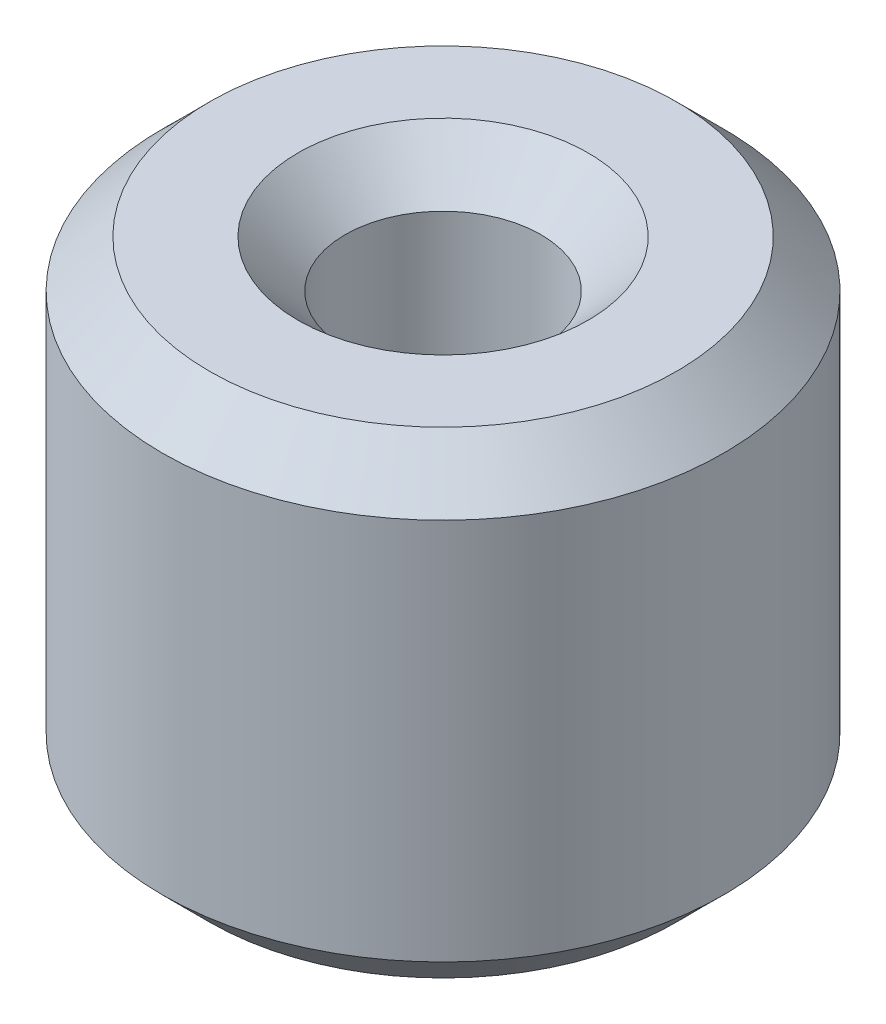
SolidWorks part; units mm, degrees
ref_plane "Front Plane" through (0, 0, 0) normal (0, 0, 1) x (1, 0, 0)
ref_plane "Top Plane" through (0, 0, 0) normal (0, 1, 0) x (1, 0, 0)
ref_plane "Right Plane" through (0, 0, 0) normal (1, 0, 0) x (0, 0, -1)
sketch "Sketch1" plane through (0, 0, 0) normal (0, 1, 0) x (1, 0, 0)
  circle A0 centre (0, 0) radius 12.5
  dimension "SLEEVE_OD" = 25
extrude "Boss-Extrude1" add sketch "Sketch1" along normal blind 21.2413
sketch "Sketch2" plane through (0, 0, 0) normal (0, 1, 0) x (1, 0, 0)
  circle A0 centre (0, 0) radius 4.3578
  dimension "BORE_D" = 8.7155
extrude "Cut-Extrude1" cut sketch "Sketch2" along normal through all
chamfer "Chamfer1" distance 2.1019 angle 45 4 edges at (0, 21.2413, 4.3578) (0, 0, 4.3578) (0, 0, 12.5) (0, 21.2413, 12.5)
